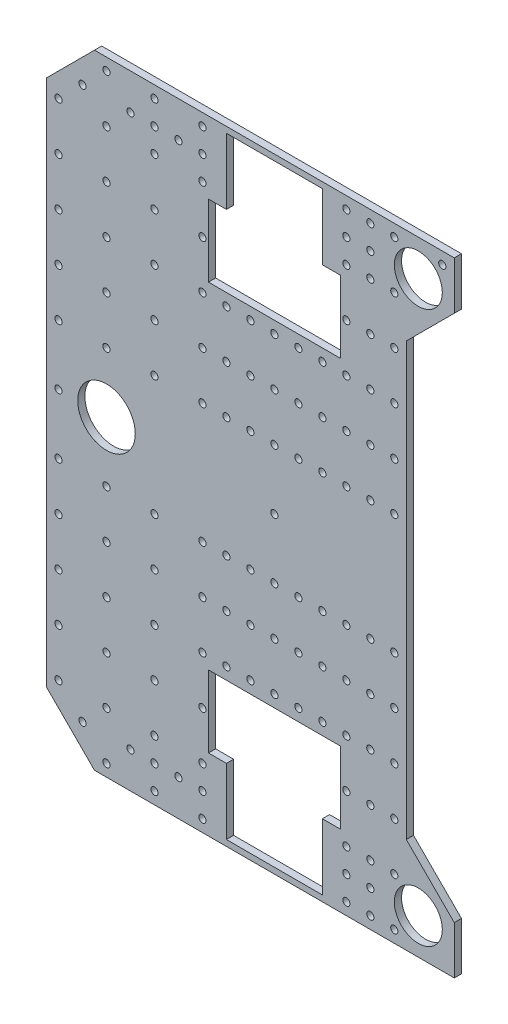
SolidWorks part; units mm, degrees
ref_plane "Front Plane" through (0, 0, 0) normal (0, 0, 1) x (1, 0, 0)
ref_plane "Top Plane" through (0, 0, 0) normal (0, 1, 0) x (1, 0, 0)
ref_plane "Right Plane" through (0, 0, 0) normal (1, 0, 0) x (0, 0, -1)
ref_axis "Axis1" through (-88.99, 0, 0) along (1, 0, 0)
ref_axis "Axis3" through (0, -55, 0) along (0, 1, 0)
sketch "Sketch1" plane through (0, 0, 0) normal (0, 0, 1) x (1, 0, 0)
  line L0 (-95, 110) -> (-95, -110)
  line L1 (-95, -110) -> (-75, -130)
  line L2 (-75, -130) -> (75, -130)
  line L3 (75, -130) -> (75, -110)
  line L4 (75, -110) -> (55, -90)
  line L5 (55, -90) -> (55, 90)
  line L6 (55, 90) -> (75, 110)
  line L7 (75, 110) -> (75, 130)
  line L8 (75, 130) -> (-75, 130)
  line L9 (-75, 130) -> (-95, 110)
  line L10 (-88.99, 0) -> (88.99, 0) construction
  circle A0 centre (93, 0) radius 38 construction
  circle A1 centre (93, -76) radius 38 construction
  circle A2 centre (93, 76) radius 38 construction
  point P2 (-95, 0)
  point P14 (-41.3479, 0)
  point P21 (0, 130)
  dimension "D15" = 76
  dimension "D1" = 220
  dimension "D2" = 150
  dimension "D3" = 20
  dimension "D4" = 20
  dimension "D5" = 20
  dimension "D6" = 95
  dimension "D7" = 20
  dimension "D8" = 180
  dimension "D9" = 150
  dimension "D10" = 28.2843
  dimension "D11" = 28.2843
  dimension "D12" = 20
  dimension "D13" = 20
  dimension "D14" = 20
extrude "Main" add sketch "Sketch1" along normal blind 3
sketch "Sketch2" plane through (0, 0, 3) normal (0, 0, 1) x (1, 0, 0)
  line L0 (-27.5, 100) -> (-27.5, 70)
  line L1 (-27.5, 70) -> (27.5, 70)
  line L2 (27.5, 70) -> (27.5, 100)
  line L3 (27.5, 100) -> (20, 100)
  line L4 (20, 100) -> (20, 127.5)
  line L5 (20, 127.5) -> (-20, 127.5)
  line L6 (-20, 127.5) -> (-20, 100)
  line L7 (-20, 100) -> (-27.5, 100)
  line L8 (0, -55) -> (0, 55) construction
  line L9 (-88.99, 0) -> (88.99, 0) construction
  point P8 (0, 70)
  dimension "D1" = 55
  dimension "D2" = 70
  dimension "D3" = 40
  dimension "D4" = 27.5
  dimension "D5" = 30
extrude "MotorCoderLeftHole" cut sketch "Sketch2" against normal through all
sketch "Sketch4" plane through (0, 0, 3) normal (0, 0, 1) x (1, 0, 0)
  circle A0 centre (-90, 105) radius 1.5
  dimension "D1" = 3
  dimension "D2" = 5
  dimension "D3" = 5
extrude "BottomLeftHole" cut sketch "Sketch4" against normal through all
pattern_linear "BottomLeftHoleLPattern" count 5 spacing 20 along (0, -1, 0) of "BottomLeftHole"
sketch "Sketch5" plane through (0, 0, 3) normal (0, 0, 1) x (1, 0, 0)
  circle A0 centre (-70, 125) radius 1.5
  circle A1 centre (-50, 125) radius 1.5
  circle A2 centre (-30, 125) radius 1.5
  circle A3 centre (30, 125) radius 1.5
  circle A4 centre (50, 125) radius 1.5
  circle A5 centre (40, 125) radius 1.5
  dimension "D3" = 3
  dimension "D5" = 3
  dimension "D6" = 3
  dimension "D8" = 60
  dimension "D9" = 3
  dimension "D10" = 3
  dimension "D12" = 3
  dimension "D1" = 5
  dimension "D2" = 5
  dimension "D4" = 20
  dimension "D7" = 20
  dimension "D11" = 20
  dimension "D13" = 10
extrude "BottomLeftHole2" cut sketch "Sketch5" against normal through all
pattern_linear "BottomLeftHole2LPattern" count 6 spacing 20 along (0, -1, 0) of "BottomLeftHole2"
sketch "Sketch6" plane through (0, 0, 3) normal (0, 0, 1) x (1, 0, 0)
  line L0 (75, 110) -> (75, 130) construction
  line L1 (75, 130) -> (-75, 130) construction
  circle A0 centre (70, 125) radius 1.5
  dimension "D1" = 3
  dimension "D2" = 5
  dimension "D3" = 5
extrude "TopLeftHole" cut sketch "Sketch6" against normal through all
sketch "Sketch7" plane through (0, 0, 3) normal (0, 0, 1) x (1, 0, 0)
  line L0 (-88.99, 0) -> (88.99, 0) construction
  line L1 (0, -55) -> (0, 55) construction
  circle A0 centre (0, 65) radius 1.5
  circle A1 centre (-10, 65) radius 1.5
  circle A2 centre (10, 65) radius 1.5
  circle A3 centre (-20, 65) radius 1.5
  circle A4 centre (20, 65) radius 1.5
  dimension "D1" = 3
  dimension "D2" = 65
  dimension "D3" = 10
  dimension "D4" = 10
  dimension "D5" = 10
  dimension "D6" = 10
extrude "MotorFixHoles" cut sketch "Sketch7" against normal through all
pattern_linear "MotorFixHoleLPattern" count 3 spacing 20 along (0, -1, 0) of "MotorFixHoles"
sketch "Sketch8" plane through (0, 0, 3) normal (0, 0, 1) x (1, 0, 0)
  line L0 (75, 130) -> (-75, 130) construction
  circle A0 centre (-80, 115) radius 1.5
  circle A1 centre (-60, 115) radius 1.5
  circle A2 centre (60, 115) radius 1.5
  circle A3 centre (-90, 105) radius 1.5 construction
  circle A4 centre (70, 125) radius 1.5 construction
  circle A5 centre (-40, 115) radius 1.5
  circle A6 centre (40, 115) radius 1.5
  circle A7 centre (-30, 115) radius 1.5
  circle A8 centre (-50, 115) radius 1.5
  circle A9 centre (30, 115) radius 1.5
  dimension "D1" = 10
  dimension "D3" = 3
  dimension "D5" = 10
  dimension "D6" = 3
  dimension "D2" = 15
  dimension "D4" = 20
  dimension "D7" = 20
  dimension "D8" = 20
  dimension "D9" = 10
  dimension "D10" = 10
  dimension "D11" = 10
extrude "CoderHole" cut sketch "Sketch8" against normal through all
mirror "Mirror1" about plane through (0, 0, 0) normal (0, 1, 0) of "CoderHole", "BottomLeftHoleLPattern", "MotorCoderLeftHole", "BottomLeftHole2LPattern", "MotorFixHoleLPattern"
sketch "Sketch3" plane through (0, 0, 3) normal (0, 0, 1) x (1, 0, 0)
  line L0 (-88.99, 0) -> (88.99, 0) construction
  line L1 (-95, 110) -> (-95, -110) construction
  line L2 (60, 115) -> (60, -115) construction
  circle A0 centre (-70, 0) radius 12
  circle A1 centre (60, 115) radius 10
  circle A2 centre (60, -115) radius 10
  circle A3 centre (0, 0) radius 1.5
  circle A4 centre (-90, 0) radius 1.5
  point P10 (45, 0)
  point P11 (60, 0)
  dimension "D1" = 24
  dimension "D3" = 20
  dimension "D6" = 3
  dimension "D2" = 25
  dimension "D7" = 5
extrude "BigHoles" cut sketch "Sketch3" against normal through all
